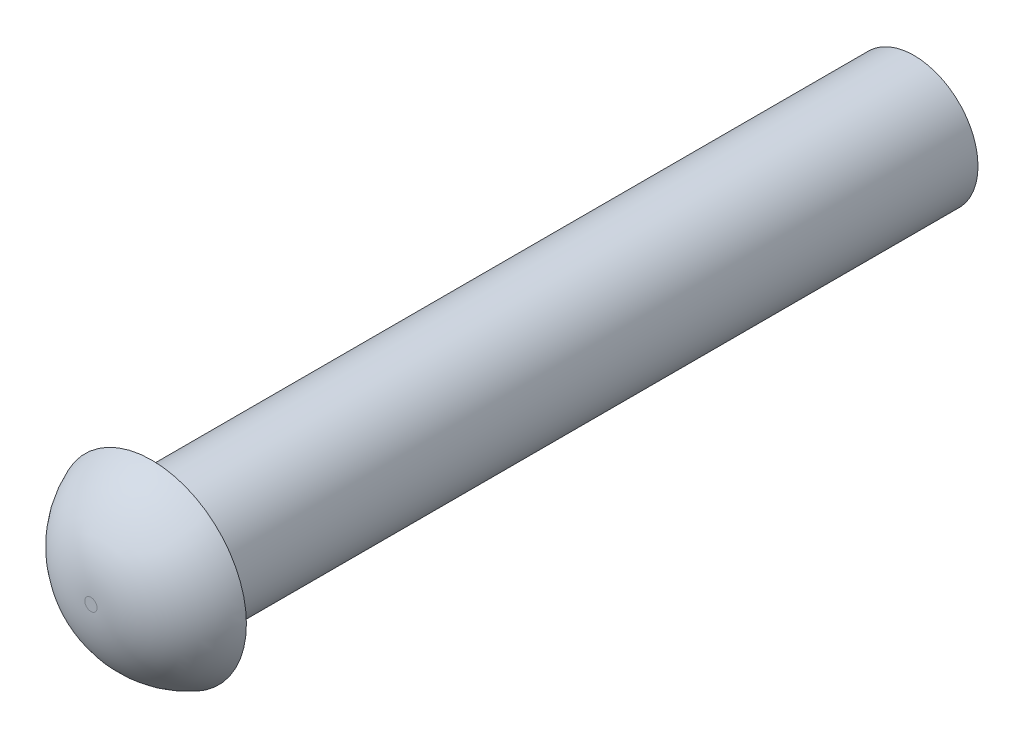
SolidWorks part; units mm, degrees
ref_plane "Płaszczyzna przednia" through (0, 0, 0) normal (0, 0, 1) x (1, 0, 0)
ref_plane "Płaszczyzna górna" through (0, 0, 0) normal (0, 1, 0) x (1, 0, 0)
ref_plane "Płaszczyzna prawa" through (0, 0, 0) normal (1, 0, 0) x (0, 0, -1)
sketch "Szkic1" plane through (0, 0, 0) normal (0, 0, 1) x (1, 0, 0)
  circle A0 centre (0, 0) radius 1.05
  dimension "D1" = 2.1
extrude "Dodanie-wyciągnięcie1" add sketch "Szkic1" along normal blind 6.5 and the other way blind 6
sketch "Szkic2" plane through (0, 0, 6.5) normal (0, 0, 1) x (1, 0, 0)
  circle A0 centre (0, 0) radius 1.55
  dimension "D1" = 3.1
extrude "Dodanie-wyciągnięcie2" add sketch "Szkic2" along normal blind 1
fillet "Zaokrąglenie1" radius 1.55 1 edges at (1.55, 0, 7.5)
